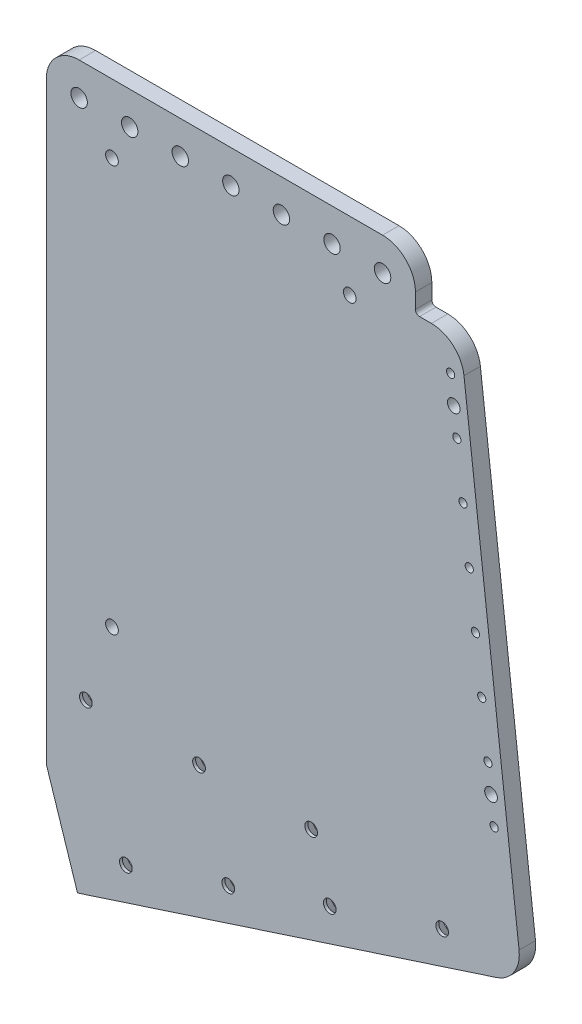
SolidWorks part; units mm, degrees
material "Acrylic (Medium-high impact)"
ref_plane "Front Plane" through (0, 0, 0) normal (0, 0, 1) x (1, 0, 0)
ref_plane "Top Plane" through (0, 0, 0) normal (0, 1, 0) x (1, 0, 0)
ref_plane "Right Plane" through (0, 0, 0) normal (1, 0, 0) x (0, 0, -1)
sketch "Sketch1" plane through (0, 0, 0) normal (0, 0, 1) x (1, 0, 0)
  line L1 (-234.753, 12.7) -> (-91.9973, 12.7)
  line L2 (-234.753, 12.7) -> (-234.753, -270.5428)
  line L3 (-234.753, -270.5428) -> (-50.7003, -210.6746)
  line L4 (-74.5335, -7.417) -> (-50.7003, -210.6746)
  line L5 (-64.9774, -197.966) -> (-88.1902, 0) construction
  line L8 (-74.5335, -7.417) -> (-91.9973, -7.417)
  line L9 (-91.9973, -7.417) -> (-91.9973, 12.7)
  line L10 (-91.9973, 0) -> (-91.9973, 12.7) construction
  dimension "D1" = 12.7
  dimension "D2" = 71.981
  dimension "D3" = 283.2428
extrude "Boss-Extrude1" add sketch "Sketch1" along normal blind 6.35
fillet "Fillet1" radius 12.7 4 edges at (-74.5335, -7.417, 3.175) (-50.7003, -210.6746, 3.175) (-234.753, 12.7, 3.175) (-91.9973, 12.7, 3.175)
sketch "Sketch2" plane through (0, 0, 6.35) normal (0, 0, 1) x (1, 0, 0)
  line L0 (-234.753, -270.5428) -> (-60.5975, -213.8939) construction
  line L1 (-234.753, 0) -> (-234.753, -270.5428) construction
  line L2 (-234.753, -270.5428) -> (-222.6758, -266.6143)
  line L3 (-234.753, -229.4856) -> (-234.753, -270.5428)
  line L4 (-222.6758, -266.6143) -> (-234.753, -229.4856)
  dimension "D1" = 12.7
extrude "Cut-Extrude1" cut sketch "Sketch2" against normal through all
hole_wizard "CSK for #8 Flat Head Machine Screw1" positions "Sketch3" profile "Sketch4" countersink size "#8" standard "ANSI Inch" end condition through all
sketch "Sketch3" plane through (0, 0, 0) normal (0, 0, -1) x (-1, 0, 0)
  point P0 (203.9698, -247.917)
  point P3 (164.3688, -235.0357)
  point P6 (175.687, -200.2402)
  point P9 (219.4388, -200.3608)
  point P12 (125.1181, -222.2683)
  point P15 (132.3222, -200.1207)
  point P18 (81.6603, -208.1325)
  point P21 (0, 0)
  point P22 (81.6603, -208.1325)
sketch "Sketch4" plane through (-203.9698, -247.917, 0) normal (1, 0, 0) x (0, 1, 0)
  line L0 (0, 0) -> (0, 6.35)
  line L1 (0, 6.35) -> (2.4574, 6.35)
  line L2 (2.4574, 6.35) -> (2.4574, 5.1984)
  line L3 (2.4574, 5.1984) -> (6.9764, 0)
  line L5 (6.9764, 0) -> (0, 0)
  line L6 (-2.4575, 5.1984) -> (-6.9764, 0) construction
  line L11 (0, -6.35) -> (0, 107.95) construction
  dimension "Thru Hole Dia." = 4.9149
  dimension "Thru Hole Depth" = 6.35
  dimension "Near C'Sink Dia." = 13.9528
  dimension "Near C'Sink Angle" = 82
sketch "Sketch5" plane through (0, 0, 6.35) normal (0, 0, 1) x (1, 0, 0)
  circle A0 centre (-90.1466, -37.8408) radius 5.5563
  circle A1 centre (-75.5767, -162.098) radius 5.5563
  dimension "D1" = 11.1125
extrude "Cut-Extrude2" [suppressed] cut sketch "Sketch5" against normal up to next
hole_wizard "1/8 (0.125) Diameter Hole1" positions "Sketch6" profile "Sketch7" hole size "1/8" standard "ANSI Inch" end condition through all
sketch "Sketch6" plane through (0, 0, 6.35) normal (0, 0, 1) x (1, 0, 0)
  line L0 (-78.3786, -20.4258) -> (-59.1514, -184.4023) construction
  line L4 (-51.9123, -200.3378) -> (-73.2177, -18.638) construction
  line L5 (-234.495, -184.8332) -> (-53.7824, -184.3891) construction
  point P1 (-78.3786, -20.4258)
  point P21 (-75.9752, -40.9228)
  point P22 (-73.5718, -61.4199)
  point P23 (-71.1684, -81.917)
  point P24 (-68.765, -102.414)
  point P25 (-66.3616, -122.9111)
  point P26 (-63.9582, -143.4082)
  point P27 (-61.5548, -163.9053)
  dimension "D1" = 5.334
  dimension "D2" = 165.1
  dimension "D3" = 8
sketch "Sketch7" plane through (-78.3786, -20.4258, 6.35) normal (1, 0, 0) x (0, -1, 0)
  line L0 (0, 0) -> (0, 6.35)
  line L1 (0, 6.35) -> (1.5875, 6.35)
  line L2 (1.5875, 6.35) -> (1.5875, 0)
  line L5 (1.5875, 0) -> (0, 0)
  line L11 (0, -6.35) -> (0, 107.95) construction
  dimension "Thru Hole Dia." = 3.175
  dimension "Thru Hole Depth" = 6.35
hole_wizard "#8 Clearance Hole1" positions "Sketch8" profile "Sketch9" hole size "#8" standard "ANSI Inch" end condition through all
sketch "Sketch8" plane through (0, 0, 6.35) normal (0, 0, 1) x (1, 0, 0)
  line L0 (-78.3786, -20.4258) -> (-75.9752, -40.9228) construction
  line L2 (-63.9582, -143.4082) -> (-61.5548, -163.9053) construction
  circle A0 centre (-78.3786, -20.4258) radius 1.5875 construction
  circle A1 centre (-75.9752, -40.9228) radius 1.5875 construction
  circle A2 centre (-63.9582, -143.4082) radius 1.5875 construction
  circle A3 centre (-61.5548, -163.9053) radius 1.5875 construction
  point P23 (-62.7565, -153.6567)
  point P25 (-77.1769, -30.6743)
sketch "Sketch9" plane through (-77.1769, -30.6743, 6.35) normal (1, 0, 0) x (0, -1, 0)
  line L0 (0, 0) -> (0, 6.35)
  line L1 (0, 6.35) -> (2.4574, 6.35)
  line L2 (2.4574, 6.35) -> (2.4574, 0)
  line L5 (2.4574, 0) -> (0, 0)
  line L11 (0, -6.35) -> (0, 107.95) construction
  dimension "Thru Hole Dia." = 4.9149
  dimension "Thru Hole Depth" = 6.35
hole_wizard "1/4 (0.25) Diameter Hole1" positions "Sketch10" profile "Sketch11" hole size "1/4" standard "ANSI Inch" end condition through all
sketch "Sketch10" plane through (0, 0, 6.35) normal (0, 0, 1) x (1, 0, 0)
  point P0 (-104.6973, 0)
  point P2 (-124.2566, 0)
  point P4 (-143.8159, 0)
  point P6 (-163.3751, 0)
  point P8 (-182.9344, 0)
  point P10 (-202.4937, 0)
  point P12 (-222.053, 0)
sketch "Sketch11" plane through (-104.6973, 0, 6.35) normal (1, 0, 0) x (0, -1, 0)
  line L0 (0, 0) -> (0, 6.35)
  line L1 (0, 6.35) -> (3.175, 6.35)
  line L2 (3.175, 6.35) -> (3.175, 0)
  line L5 (3.175, 0) -> (0, 0)
  line L11 (0, -6.35) -> (0, 107.95) construction
  dimension "Thru Hole Dia." = 6.35
  dimension "Thru Hole Depth" = 6.35
hole_wizard "#8 Clearance Hole2" positions "Sketch12" profile "Sketch13" hole size "#8" standard "ANSI Inch" end condition through all
sketch "Sketch12" plane through (0, 0, 6.35) normal (0, 0, 1) x (1, 0, 0)
  point P1 (-117.3973, -13.767)
  point P3 (-209.353, -13.767)
sketch "Sketch13" plane through (-117.3973, -13.767, 6.35) normal (1, 0, 0) x (0, -1, 0)
  line L0 (0, 0) -> (0, 6.35)
  line L1 (0, 6.35) -> (2.4574, 6.35)
  line L2 (2.4574, 6.35) -> (2.4574, 0)
  line L5 (2.4574, 0) -> (0, 0)
  line L11 (0, -6.35) -> (0, 107.95) construction
  dimension "Thru Hole Dia." = 4.9149
  dimension "Thru Hole Depth" = 6.35
hole_wizard "#8 Clearance Hole3" positions "Sketch14" profile "Sketch15" hole size "#8" standard "ANSI Inch" end condition through all
sketch "Sketch14" plane through (0, 0, 6.35) normal (0, 0, 1) x (1, 0, 0)
  line L0 (-209.353, -13.767) -> (-209.353, -262.2807) construction
  line L1 (-222.6758, -266.6143) -> (-60.5975, -213.8939) construction
  line L2 (-62.7565, -153.6567) -> (-209.353, -170.8461) construction
  line L4 (-51.9123, -200.3378) -> (-73.2177, -18.638) construction
  circle A0 centre (-209.353, -13.767) radius 2.4574 construction
  point P0 (-209.353, -170.8461)
  point P24 (-209.353, -170.8479)
  point P25 (-209.353, -170.8461)
sketch "Sketch15" plane through (-209.353, -170.8461, 6.35) normal (1, 0, 0) x (0, -1, 0)
  line L0 (0, 0) -> (0, 6.35)
  line L1 (0, 6.35) -> (2.4574, 6.35)
  line L2 (2.4574, 6.35) -> (2.4574, 0)
  line L5 (2.4574, 0) -> (0, 0)
  line L11 (0, -6.35) -> (0, 107.95) construction
  dimension "Thru Hole Dia." = 4.9149
  dimension "Thru Hole Depth" = 6.35
fillet "Fillet2" radius 1.5875 1 edges at (-91.9973, -7.417, 3.175)
